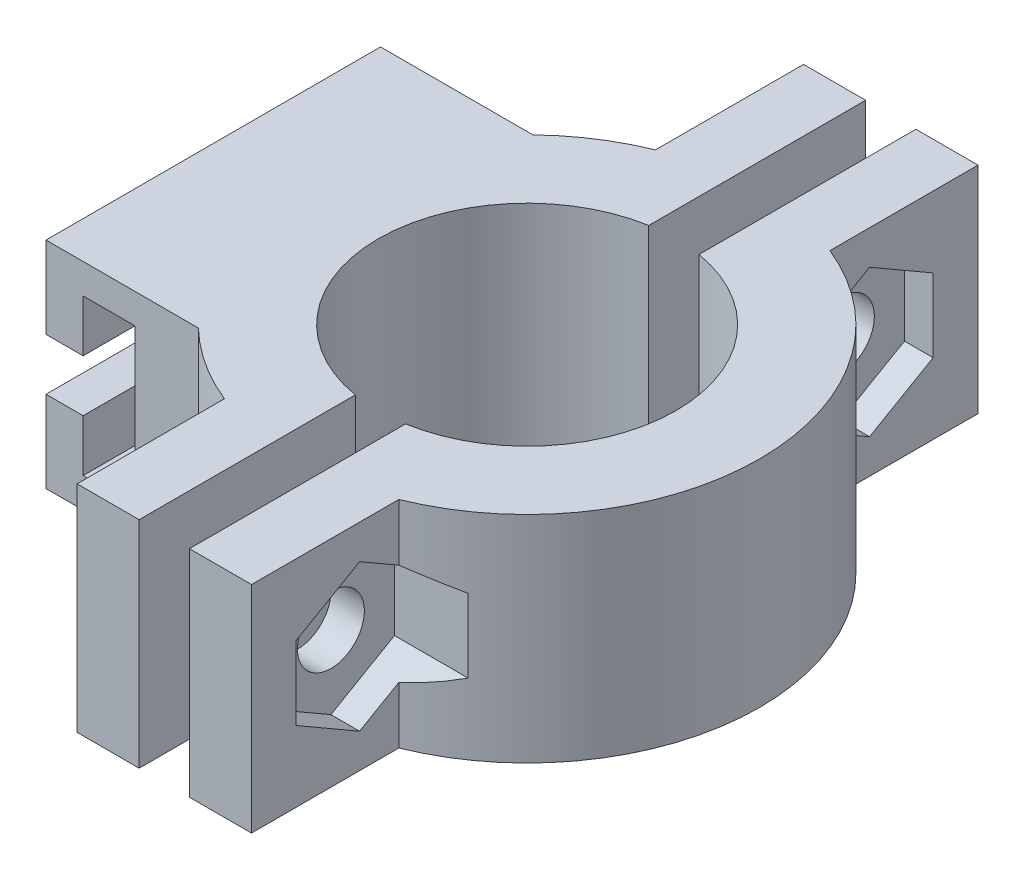
SolidWorks part; units mm, degrees
ref_plane "Front Plane" through (0, 0, 0) normal (0, 0, 1) x (1, 0, 0)
ref_plane "Top Plane" through (0, 0, 0) normal (0, 1, 0) x (1, 0, 0)
ref_plane "Right Plane" through (0, 0, 0) normal (1, 0, 0) x (0, 0, -1)
sketch "Sketch1" plane through (0, 0, 0) normal (0, 1, 0) x (1, 0, 0)
  line L9 (-1.908, -27.5493) -> (1.908, -27.5493) construction
  line L15 (1.908, -27.5493) -> (6.6227, -27.5493)
  line L16 (1.908, -27.5493) -> (1.908, -11.1408)
  line L17 (1.908, 27.6094) -> (6.6227, 27.6094)
  line L18 (6.6227, -27.5493) -> (6.6227, -16.3636)
  line L19 (-6.6227, -27.5493) -> (-1.908, -27.5493)
  line L20 (-6.6227, -27.5493) -> (-6.6227, -16.3636)
  line L21 (-6.6227, 27.6094) -> (-1.908, 27.6094)
  line L22 (-1.908, -27.5493) -> (-1.908, -11.1408)
  line L23 (-1.908, 27.6094) -> (1.908, 27.6094) construction
  line L25 (-6.6227, 16.3636) -> (-6.6227, 27.6094)
  line L26 (-1.908, 11.1408) -> (-1.908, 27.6094)
  line L27 (6.6227, 16.3636) -> (6.6227, 27.6094)
  line L28 (1.908, 11.1408) -> (1.908, 27.6094)
  arc A0 (6.6227, -16.3636) -> (6.6227, 16.3636) centre (0, 0) ccw
  arc A1 (1.908, -11.1408) -> (1.908, 11.1408) centre (0, 0) ccw
  arc A2 (-1.908, 11.1408) -> (-1.908, -11.1408) centre (0, 0) ccw
  arc A3 (-6.6227, 16.3636) -> (-6.6227, -16.3636) centre (0, 0) ccw
  point P24 (0, -27.5493)
  dimension "D1" = 22.606
  dimension "D2" = 6.35
extrude "Boss-Extrude1" add sketch "Sketch1" along normal blind 16.3437 contours A0 | A0 | A1 L16 L15 L18 A0 L27 L17 L28 | L25 A3 L20 L19 L22 A2 L26 L21 region at (2.4816, 0, 19.345) region at (-6.0491, 0, 21.9564)
sketch "Sketch2" plane through (1.908, 0, 1.908) normal (1, 0, 0) x (0, 0, -1)
  line L1 (21.2831, 2.5993) -> (26.1091, 5.3856)
  line L2 (26.1091, 5.3856) -> (26.1091, 10.9582)
  line L3 (26.1091, 10.9582) -> (21.2831, 13.7444)
  line L4 (21.2831, 13.7444) -> (16.4571, 10.9582)
  line L5 (16.4571, 10.9582) -> (16.4571, 5.3856)
  line L6 (16.4571, 5.3856) -> (21.2831, 2.5993)
  line L7 (-17.437, 2.5993) -> (-12.611, 5.3856)
  line L16 (-12.611, 5.3856) -> (-12.611, 10.9582)
  line L17 (-12.611, 10.9582) -> (-17.437, 13.7444)
  line L18 (13.0488, 0) -> (29.5174, 0)
  line L20 (13.0488, 16.3437) -> (13.0488, 0)
  line L21 (29.5174, 16.3437) -> (13.0488, 16.3437)
  line L22 (29.5174, 0) -> (29.5174, 16.3437)
  line L32 (13.0488, 0) -> (29.5174, 0)
  line L33 (13.0488, 16.3437) -> (13.0488, 0)
  line L34 (29.5174, 16.3437) -> (13.0488, 16.3437)
  line L35 (29.5174, 0) -> (29.5174, 16.3437)
  line L36 (-25.6412, 0) -> (-9.2328, 0)
  line L37 (-25.6412, 16.3437) -> (-25.6412, 0)
  line L38 (-9.2328, 16.3437) -> (-25.6412, 16.3437)
  line L39 (-9.2328, 0) -> (-9.2328, 16.3437)
  line L40 (-25.6412, 0) -> (-9.2328, 0)
  line L41 (-25.6412, 16.3437) -> (-25.6412, 0)
  line L42 (-9.2328, 16.3437) -> (-25.6412, 16.3437)
  line L43 (-9.2328, 0) -> (-9.2328, 16.3437)
  line L44 (-17.437, 13.7444) -> (-22.263, 10.9582)
  line L45 (-22.263, 10.9582) -> (-22.263, 5.3856)
  line L46 (-22.263, 5.3856) -> (-17.437, 2.5993)
  circle A0 centre (21.2831, 8.1719) radius 2.54
  circle A4 centre (21.2831, 8.1719) radius 6.35
  circle A5 centre (21.2831, 8.1719) radius 4.826 construction
  circle A6 centre (-17.437, 8.1719) radius 6.35
  circle A7 centre (-17.437, 8.1719) radius 4.826 construction
  circle A8 centre (-17.437, 8.1719) radius 2.54
  point P20 (21.2831, 0)
  point P23 (13.0488, 8.1719)
  point P30 (-17.437, 0)
  point P32 (-25.6412, 8.1719)
  dimension "D1" = 0
  dimension "D2" = 12.7
  dimension "D5" = 5.08
  dimension "D3" = 9.652
  dimension "D4" = 0
extrude "Cut-Extrude1" cut sketch "Sketch2" along normal blind 11.43 from offset 2.54 contours L2 L3 L4 L5 L6 L1 | L16 L17 L44 L45 L46 L7
sketch "Sketch3" plane through (0, 0, 0) normal (0, 0, 1) x (1, 0, 0)
  line L2 (-6.6227, 16.3437) -> (-1.908, 16.3437)
  line L4 (-6.6227, 16.3437) -> (-1.908, 16.3437)
  line L6 (-1.908, 16.3437) -> (-1.908, 0)
  line L13 (-11.9572, 0) -> (-23.8312, 0)
  line L14 (-11.9572, 0) -> (-11.9572, 16.3437)
  line L15 (-11.9572, 16.3437) -> (-23.8312, 16.3437)
  line L16 (-23.8312, 0) -> (-23.8312, 16.3437)
  line L17 (-23.8312, 6.2034) -> (-21.0118, 6.2034)
  line L18 (-23.8312, 6.2034) -> (-23.8312, 10.1404)
  line L19 (-23.8312, 10.1404) -> (-21.0118, 10.1404)
  line L20 (-21.0118, 6.2034) -> (-21.0118, 10.1404)
  line L21 (-21.0118, 2.2664) -> (-17.0748, 2.2664)
  line L22 (-21.0118, 2.2664) -> (-21.0118, 14.0774)
  line L23 (-21.0118, 14.0774) -> (-17.0748, 14.0774)
  line L24 (-17.0748, 2.2664) -> (-17.0748, 14.0774)
  line L25 (-1.908, 16.3437) -> (-1.908, 0)
  line L26 (-1.908, 0) -> (-6.6227, 0)
  line L27 (-1.908, 0) -> (-6.6227, 0)
  line L28 (-6.6227, 0) -> (-17.653, 0)
  line L29 (-6.6227, 0) -> (-17.653, 0)
  line L30 (-17.653, 0) -> (-17.653, 16.3437)
  line L31 (-17.653, 0) -> (-17.653, 16.3437)
  line L32 (-17.653, 16.3437) -> (-6.6227, 16.3437)
  line L33 (-17.653, 16.3437) -> (-6.6227, 16.3437)
  line L34 (1.908, 16.3437) -> (6.6227, 16.3437)
  line L35 (1.908, 16.3437) -> (6.6227, 16.3437)
  line L36 (6.6227, 16.3437) -> (17.653, 16.3437)
  line L37 (6.6227, 16.3437) -> (17.653, 16.3437)
  line L38 (17.653, 16.3437) -> (17.653, 0)
  line L39 (17.653, 16.3437) -> (17.653, 0)
  line L40 (17.653, 0) -> (6.6227, 0)
  line L41 (17.653, 0) -> (6.6227, 0)
  line L42 (6.6227, 0) -> (1.908, 0)
  line L44 (1.908, 0) -> (1.908, 16.3437)
  line L45 (1.908, 0) -> (1.908, 16.3437)
  line L50 (6.6227, 0) -> (1.908, 0)
  point P18 (-23.8312, 8.1719)
  point P19 (-23.8312, 8.1719)
  point P20 (-21.0118, 8.1719)
  point P27 (-11.9572, 0)
  dimension "D1" = 3.937
  dimension "D2" = 3.937
  dimension "D3" = 11.811
  dimension "D4" = 2.8194
extrude "Boss-Extrude2" add sketch "Sketch3" along normal blind 12.7 and the other way blind 12.7 contours L21 L22 L17 L16 L13 | L24 L21 L14 L23 | L22 L23 L15 L16 L19 region at (-14.6025, 8.1719, 0) region at (-21.4847, 13.839, 0) region at (-21.4847, 2.5047, 0)
extrude "Cut-Extrude5" cut sketch "Sketch3<3>" against normal through all both and the other way through all contours L23 L22 L20 L21 | L17 L20 L19 L16 | L21 L24 L23 region at (-19.3324, 8.1719, 0) region at (-17.3639, 8.1719, 0) region at (-22.4215, 8.1719, 0)
sketch "Sketch3<3>" plane through (0, 0, 0) normal (0, 0, 1) x (1, 0, 0) same geometry as "Sketch3"
extrude "Cut-Extrude6" cut sketch "Sketch2<7>" against normal through all both and the other way through all contours A8 | A0
sketch "Sketch2<7>" plane through (1.908, 0, 1.908) normal (1, 0, 0) x (0, 0, -1) same geometry as "Sketch2"
extrude "Cut-Extrude7" cut sketch "Sketch2<8>" against normal blind 24.638 from surface contours A6 | A4 starting at face at (-6.6227, 8.1719, -16.8351)
sketch "Sketch2<8>" plane through (1.908, 0, 1.908) normal (1, 0, 0) x (0, 0, -1) same geometry as "Sketch2"
